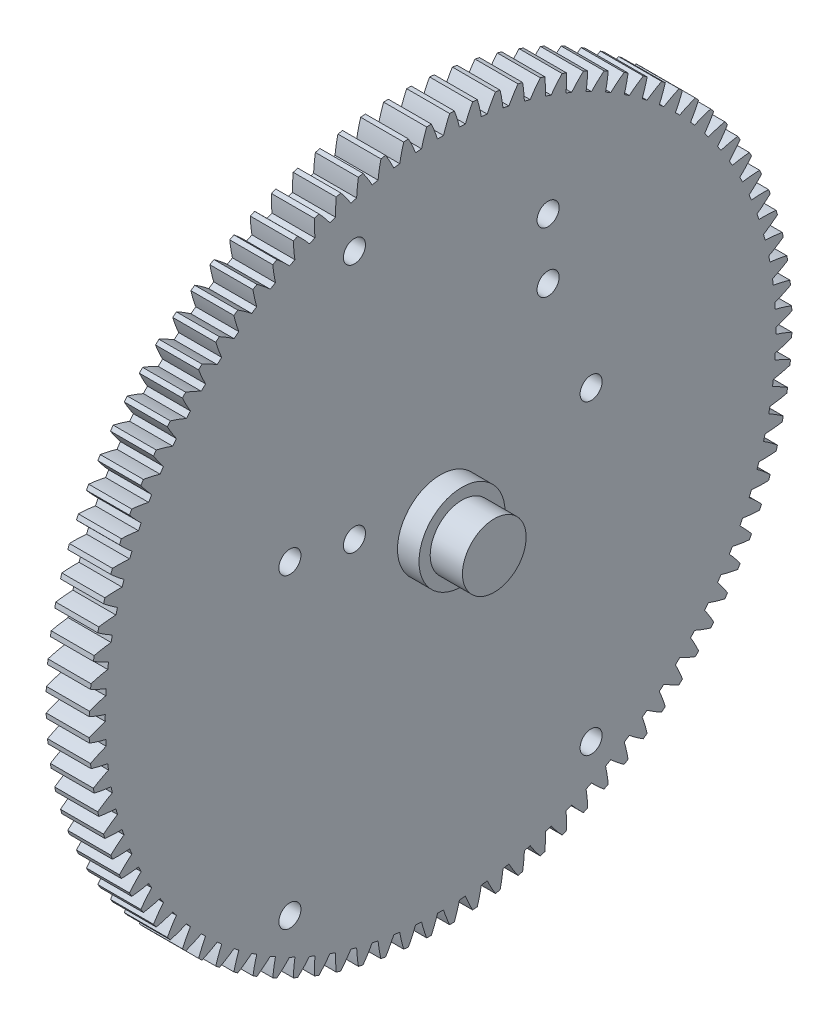
SolidWorks part; units mm, degrees
ref_plane "Plane1" through (0, 0, 0) normal (0, 0, 1) x (1, 0, 0)
ref_plane "Plane2" through (0, 0, 0) normal (0, 1, 0) x (1, 0, 0)
ref_plane "Plane3" through (0, 0, 0) normal (1, 0, 0) x (0, 0, -1)
other "Configuration Table"
sketch "HoldingSke" plane through (0, 0, 0) normal (0, 1, 0) x (1, 0, 0)
  line L0 (0, 0) -> (-31.8603, -303.1303)
  line L1 (-15, 0) -> (100, 0) construction
  line L2 (0, 0) -> (-2.1039, 2.3779)
  line L3 (0, 0) -> (-11.863, 4.5341)
  line L4 (0, 0) -> (-0.9027, 8.5887)
  line L5 (0, 0) -> (-47.5972, -17.7524)
  line L6 (0, 0) -> (-10.5278, -7.1032)
  line L7 (-2.1039, 2.3779) -> (8.8308, 51.9871)
  line L8 (-76.2, 54.61) -> (-54.9402, 54.61)
  line L9 (-71.009, 38.7566) -> (-53.1078, 45.2721)
  line L10 (-76.2, 71.12) -> (104.1128, 71.12)
  line L11 (0, 0) -> (-12.7, 0)
  line L12 (-76.2, 101.6) -> (-76.1147, 101.6)
  line L13 (24.9733, 27.94) -> (52.9518, 28.4284)
  line L14 (24.9733, 27.94) -> (24.9746, 27.94)
  line L15 (24.9733, 27.94) -> (100.4006, 29.5858)
  circle A0 centre (0, 0) radius 9.525
  circle A1 centre (0, 0) radius 38.1
  circle A2 centre (0, 0) radius 38.1
  circle A3 centre (0, 0) radius 9.525
  dimension "MHD" = 76.2
  dimension "Hub_dia" = 76.2
  dimension "Bore" = 19.05
  dimension "MBD" = 19.05
  dimension "Num_teeth" = 96
  dimension "Pitch" = 304.8
  dimension "Overall_len" = 50.8
  dimension "Show_teeth" = 96
  dimension "Thickness" = 12.7
  dimension "OAL" = 50.8001
  dimension "T_dim" = 21.2598
  dimension "Ap" = 20
  dimension "H" = 19.05
  dimension "Pitch_radius" = 180.3128
  dimension "Width" = 12.7
  dimension "Backlash" = 0.0853
  dimension "Addendum_fac" = 1
  dimension "Dedendum_fac" = 1.25
  dimension "Clearance_fac" = 0.25
  dimension "Dedendum_add" = 0.0013
sketch "BasProSke" plane through (0, 0, 0) normal (0, 1, 0) x (1, 0, 0)
  line L0 (-10, 0) -> (60, 0) construction
  line L1 (0, 0) -> (0, 103.7167)
  line L2 (0, 0) -> (12.7, 0)
  line L3 (12.7, 0) -> (12.7, 103.7167)
  line L4 (12.7, 103.7167) -> (0, 103.7167)
  dimension "Thickness" = 12.7
  dimension "Diameter" = 207.4333
revolve "Base-Revolve" add sketch "BasProSke" angle 360 about L0
sketch "TooCutSke" plane through (0, 0, 0) normal (1, 0, 0) x (0, 0, -1)
  line L1 (0, 0) -> (0, 107) construction
  line L2 (0, 0) -> (-1.8117, 101.5838) construction
  line L3 (0, 0) -> (-6.6478, 203.0687) construction
  line L4 (-1.8117, 101.5838) -> (-3.3239, 101.5343) construction
  arc A0 (0.8885, 98.9489) -> (-0.8885, 98.9489) centre (0, 0) ccw
  arc A1 (2.7086, 103.7067) -> (-2.7086, 103.7067) centre (0, 0) ccw
  circle A2 centre (0, 0) radius 101.6 construction
  circle A3 centre (0, 0) radius 95.4728 construction
  arc A4 (-0.8885, 98.9489) -> (-2.7086, 103.7067) centre (-39.6813, 86.8358) ccw
  arc A5 (2.7086, 103.7067) -> (0.8885, 98.9489) centre (39.6813, 86.8358) ccw
  dimension "Root_dia" = 197.9058
  dimension "Overcut_dia" = 207.4841
  dimension "Pitch_dia" = 203.2
  dimension "Base_dia" = 190.9455
  dimension "Flank_rad" = 40.64
  dimension "Half_ang" = 1.875
  dimension "Half_CT" = 1.513
extrude "ToothCut" cut sketch "TooCutSke" along normal through all
fillet "Breaks" [suppressed] radius 0.0423 tangent propagation no
fillet "RootFillets" [suppressed] radius 0.5304
pattern_circular "TeethCuts" count 96 every 3.75 about axis through (-10, 0, 0) along (1, 0, 0) of "ToothCut", "RootFillets", "Breaks"
sketch "HubNeaOneSke" plane through (0, 0, 0) normal (-1, 0, 0) x (0, 0, 1)
  circle A0 centre (0, 0) radius 38.1
  dimension "Diameter" = 76.2
extrude "HubNearOne" [suppressed] add sketch "HubNeaOneSke" along normal blind 38.1001
sketch "HubNeaBotSke" plane through (0, 0, 0) normal (-1, 0, 0) x (0, 0, 1)
  circle A0 centre (0, 0) radius 38.1
  dimension "Diameter" = 76.2
extrude "HubNearBoth" [suppressed] add sketch "HubNeaBotSke" along normal blind 19.05
ref_plane "FarPln" through (12.7, 0, 0) normal (1, 0, 0) x (0, 0, -1)
sketch "HubFarSke" plane through (12.7, 0, 0) normal (1, 0, 0) x (0, 0, -1)
  circle A0 centre (0, 0) radius 38.1
  dimension "Diameter" = 76.2
extrude "HubFar" [suppressed] add sketch "HubFarSke" along normal blind 19.05
sketch "Sketch1" plane through (12.7, 0, 0) normal (1, 0, 0) x (0, 0, -1)
  circle A0 centre (0, 0) radius 12.7
  dimension "D1" = 25.4
extrude "Boss-Extrude1" add sketch "Sketch1" along normal blind 6.35
sketch "Sketch2" plane through (19.05, 0, 0) normal (1, 0, 0) x (0, 0, -1)
  circle A0 centre (0, 0) radius 9.398
  dimension "D1" = 18.796
extrude "Boss-Extrude2" add sketch "Sketch2" along normal blind 9.525
sketch "Sketch3" plane through (0, 0, 0) normal (-1, 0, 0) x (0, 0, 1)
  line L1 (0, 0) -> (0, 44.0129) construction
  circle A0 centre (44.45, 12.7) radius 3.2512
  circle A1 centre (44.45, -77.724) radius 3.2512
  circle A2 centre (-44.45, 12.7) radius 3.2512
  circle A3 centre (-44.45, -77.724) radius 3.2512
  circle A5 centre (25.4, 82.55) radius 3.2512
  circle A6 centre (25.4, 8.89) radius 3.2512
  circle A7 centre (-31.75, 63.5) radius 3.2512
  circle A8 centre (-31.75, 45.72) radius 3.2512
  point P8 (0, 0)
  point P22 (0, 0)
  dimension "D1" = 6.5024
  dimension "D2" = 6.5024
  dimension "D6" = 6.5024
  dimension "D7" = 6.5024
  dimension "D11" = 6.5024
  dimension "D12" = 6.5024
  dimension "D3" = 90.424
  dimension "D4" = 44.45
  dimension "D5" = 12.7
  dimension "D8" = 73.66
  dimension "D9" = 25.4
  dimension "D10" = 82.55
  dimension "D13" = 17.78
  dimension "D14" = 63.5
  dimension "D15" = 31.75
extrude "Cut-Extrude1" cut sketch "Sketch3" against normal through all
equation "' \"Pitch@HoldingSke\" = 4"
equation "' \"Num_teeth@HoldingSke\" = 12"
equation "' \"Ap@HoldingSke\" =  20"
equation "' \"Ap@HoldingSke\" = 20"
equation "' \"Width@HoldingSke\" = 0.5"
equation "' \"Hub_dia@HoldingSke\"= 1"
equation "' \"Hub_dia@HoldingSke\" = 1"
equation "' \"Overall_len@HoldingSke\" = 1.0"
equation "' \"Bore@HoldingSke\" = 0.75"
equation "' \"T_dim@HoldingSke\" = 0.85"
equation "' \"Width@KeySke\" = 0.25"
equation "' \"Show_teeth@HoldingSke\" = 13"
equation "' \"Backlash@HoldingSke\" = 0.009"
equation "' \"Addendum_fac@HoldingSke\" = 1.0"
equation "' \"Dedendum_fac@HoldingSke\" = 1.25"
equation "' \"Dedendum_add@HoldingSke\" = 0.00005"
equation "' \"Clearance_fac@HoldingSke\" = 0.25"
equation "' \"Pitch@HoldingSke\" = 0.5"
equation "' \"Num_teeth@HoldingSke\" = 23"
equation "' \"Show_teeth@HoldingSke\" = 23"
equation "' \"Backlash@HoldingSke\" = 0.0375"
equation "\"Overcut_dia@TooCutSke\" = (\"Num_teeth@HoldingSke\" + 2 * \"Addendum_fac@HoldingSke\") / \"Pitch@HoldingSke\" + 0.002"
equation "\"Pitch_dia@TooCutSke\" = \"Num_teeth@HoldingSke\" / \"Pitch@HoldingSke\""
equation "\"Base_dia@TooCutSke\" = \"Num_teeth@HoldingSke\" / \"Pitch@HoldingSke\" * cos((\"Ap@HoldingSke\"  * 3.14159265 / 180))"
equation "\"Root_dia@TooCutSke\" = (\"Num_teeth@HoldingSke\" + 2) / \"Pitch@HoldingSke\" - 2 * (\"Addendum_fac@HoldingSke\" + \"Dedendum_fac@HoldingSke\") / \"Pitch@HoldingSke\" - \"Dedendum_add@HoldingSke\" * 2"
equation "\"Half_ang@TooCutSke\" = 180 / \"Num_teeth@HoldingSke\""
equation "\"Half_CT@TooCutSke\" = \"Num_teeth@HoldingSke\" / \"Pitch@HoldingSke\" * sin((3.14159265 / 2 / \"Num_teeth@HoldingSke\")) / 2 - 7 * \"Backlash@HoldingSke\" / 4"
equation "\"Flank_rad@TooCutSke\" = \"Num_teeth@HoldingSke\" / \"Pitch@HoldingSke\" / 5"
equation "\"Radius@RootFillets\" = \"Clearance_fac@HoldingSke\" / \"Pitch@HoldingSke\" + \"Dedendum_add@HoldingSke\""
equation "\"Break_rad@Breaks\" = 0.02 / \"Pitch@HoldingSke\""
equation "\"Thickness@HoldingSke\" = \"Width@HoldingSke\""
equation "\"OAL@HoldingSke\" = \"Thickness@HoldingSke\""
equation "\"MHD@HoldingSke\" = (\"Num_teeth@HoldingSke\" + 2) / \"Pitch@HoldingSke\" - 2 * (\"Addendum_fac@HoldingSke\" + \"Dedendum_fac@HoldingSke\")  / \"Pitch@HoldingSke\" - \"Dedendum_add@HoldingSke\" * 2"
equation "\"MBD@HoldingSke\" = (\"Num_teeth@HoldingSke\" + 2) / \"Pitch@HoldingSke\" - 2 * (\"Addendum_fac@HoldingSke\" + \"Dedendum_fac@HoldingSke\")  / \"Pitch@HoldingSke\" - \"Dedendum_add@HoldingSke\" * 2 - 0.002"
equation "\"MHD@HoldingSke\" = ((sgn( \"MHD@HoldingSke\" - \"Hub_dia@HoldingSke\" )-1)*( \"MHD@HoldingSke\" - \"Hub_dia@HoldingSke\" ))/-2+ \"Hub_dia@HoldingSke\""
equation "\"MBD@HoldingSke\" = ((sgn( \"MBD@HoldingSke\" - \"Bore@HoldingSke\" )-1)*( \"MBD@HoldingSke\" - \"Bore@HoldingSke\" ))/-2+ \"Bore@HoldingSke\""
equation "\"OAL@HoldingSke\" = ((sgn( \"OAL@HoldingSke\" - \"Overall_len@HoldingSke\" )+1)*( \"OAL@HoldingSke\" - \"Overall_len@HoldingSke\" ))/2 + \"Overall_len@HoldingSke\" + 0.000002"
equation "\"Num_teeth@TeethCuts\" = int( \"Show_teeth@HoldingSke\" ) + 1"
equation "\"Num_teeth@TeethCuts\" = ((sgn( \"Num_teeth@TeethCuts\" - \"Num_teeth@HoldingSke\" )-1)*( \"Num_teeth@TeethCuts\" - \"Num_teeth@HoldingSke\" ))/-2+ \"Num_teeth@HoldingSke\""
equation "\"Num_teeth@TeethCuts\" = ((sgn( \"Num_teeth@TeethCuts\" - 2.0)+1)*( \"Num_teeth@TeethCuts\" - 2.0))/2 +2.0"
equation "\"Angle@TeethCuts\" = 360.0 / \"Num_teeth@HoldingSke\""
equation "\"Diameter@BasProSke\" = (\"Num_teeth@HoldingSke\" + 2 * \"Addendum_fac@HoldingSke\") / \"Pitch@HoldingSke\""
equation "\"Thickness@BasProSke\"  = \"Thickness@HoldingSke\""
equation "' \"Fillet_rad@BasProSke\" =  \"Thickness@HoldingSke\" * 0.05"
equation "' \"Fillet_rad@BasProSke\" = \"Thickness@HoldingSke\" * 0.05"
equation "\"MHD@HoldingSke\" = ((sgn( \"MHD@HoldingSke\" - \"Root_dia@TooCutSke\" )-1)*( \"MHD@HoldingSke\" - \"Root_dia@TooCutSke\" ))/-2+ \"Root_dia@TooCutSke\""
equation "\"Diameter@HubNeaOneSke\" = \"MHD@HoldingSke\""
equation "\"Length@HubNearOne\" = \"OAL@HoldingSke\" - \"Thickness@BasProSke\""
equation "\"Diameter@HubNeaBotSke\" = \"MHD@HoldingSke\""
equation "\"Length@HubNearBoth\" = ( \"OAL@HoldingSke\" - \"Thickness@BasProSke\" ) / 2.0"
equation "\"Thickness@FarPln\" = \"Thickness@BasProSke\""
equation "\"Diameter@HubFarSke\" = \"MHD@HoldingSke\""
equation "\"Length@HubFar\" = ( \"OAL@HoldingSke\" - \"Thickness@BasProSke\" ) / 2.0"
equation "\"Diameter@BorSke\" = \"MBD@HoldingSke\""
equation "\"D1@Bore\" = \"OAL@HoldingSke\" * 2.0"
equation "\"D1@Keyway\" = \"OAL@HoldingSke\" * 2.0"
equation "\"Offset@KeySke\" = \"T_dim@HoldingSke\" - \"MBD@HoldingSke\" / 2.0"
